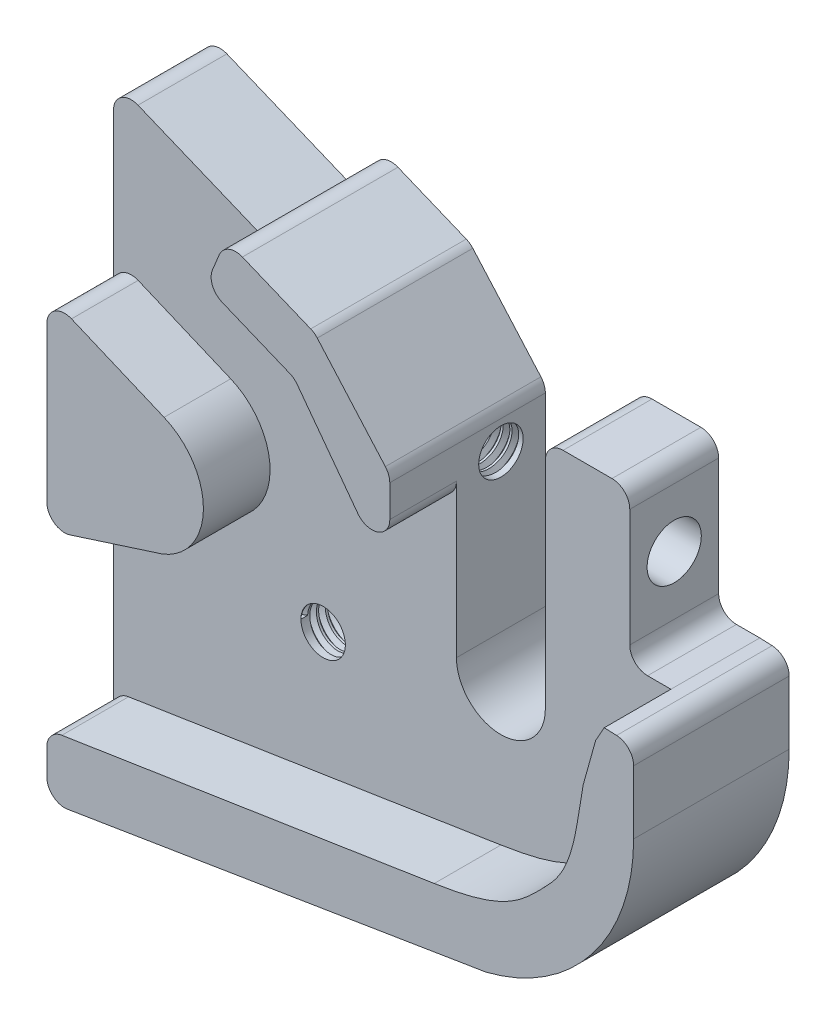
SolidWorks part; units mm, degrees
ref_plane "Front Plane" through (0, 0, 0) normal (0, 0, 1) x (1, 0, 0)
ref_plane "Top Plane" through (0, 0, 0) normal (0, 1, 0) x (1, 0, 0)
ref_plane "Right Plane" through (0, 0, 0) normal (1, 0, 0) x (0, 0, -1)
sketch "Sketch1" plane through (0, 0, 0) normal (0, 0, 1) x (1, 0, 0)
  line L0 (-48.8998, -64.1664) -> (-34.4801, 53.9567) construction
  line L3 (0, 51.4823) -> (78.4652, 51.4823)
  line L4 (78.4652, 0) -> (78.4652, 51.4823)
  line L5 (-0.9054, 14.8469) -> (9.0946, 14.8469)
  line L6 (9.0946, 14.8469) -> (9.0946, -2.1531)
  line L7 (9.0946, -2.1531) -> (-0.9054, -2.1531)
  line L8 (-0.9054, -2.1531) -> (-0.9054, 14.8469)
  line L9 (-11.6542, 28.4583) -> (-0.9054, 14.02)
  line L10 (-52.5896, 45.2866) -> (-11.6542, 28.4583)
  line L11 (9.0946, 14.8469) -> (9.0946, 29.052)
  line L12 (9.0946, 29.052) -> (18.5946, 29.052)
  line L13 (-61.5112, 32.1478) -> (-26.3036, 17.3197)
  line L14 (-26.3036, 17.3197) -> (-29.1124, 10.6505)
  line L15 (-29.1124, 10.6505) -> (-31.9213, 3.9813)
  line L16 (-70.304, -10.1797) -> (-26.4323, 3.9286)
  line L17 (-39.4934, 22.8747) -> (-39.4934, -0.2716)
  line L18 (-26.4323, 3.9286) -> (-29.1124, 10.6505)
  line L19 (-29.1124, 10.6505) -> (-31.7926, 17.3724)
  line L20 (4.0946, -12.9031) -> (-39.4934, -19.6726)
  line L22 (23.2246, 11.8381) -> (22.2572, 10.123)
  line L23 (23.2246, 11.8381) -> (34.7443, 11.3546)
  line L24 (-0.9054, 14.8469) -> (-0.9054, 20.5391)
  line L25 (-19.3381, 38.1043) -> (-8.9222, 33.8224)
  line L26 (-11.6542, 28.4583) -> (-9.3728, 34.0076)
  line L27 (-7.3088, 22.6214) -> (-2.496, 26.2043)
  line L28 (-2.496, 26.2043) -> (-9.3728, 34.0076)
  line L29 (-70.5009, -25.054) -> (-69.6167, -30.4821)
  line L31 (26.529, 2.6512) -> (26.529, -15.9236)
  line L32 (27.019, 6.583) -> (34.7443, 6.583)
  line L33 (34.7443, 6.583) -> (34.7443, 11.3546)
  line L34 (-11.6542, 28.4583) -> (-8.9222, 28.4583)
  line L35 (-70.5009, -25.054) -> (-70.304, -10.1797)
  line L36 (18.5946, 29.052) -> (18.5946, 11.8381)
  line L37 (-39.4934, -0.2716) -> (-39.4934, -26.678)
  line L38 (-39.4934, 22.8747) -> (-39.4934, 39.9028)
  line L39 (22.2572, 10.123) -> (21.4546, 7.2463)
  line L40 (21.4546, 7.2463) -> (20.8501, 5.08)
  line L41 (20.8501, 5.08) -> (20.5233, 3.0772)
  line L42 (-8.9222, 28.4583) -> (-8.9222, 25.2921)
  line L43 (-19.3381, 38.1043) -> (-21.6194, 32.5549)
  line L44 (-0.9054, 20.5391) -> (-0.9054, 24.0677)
  line L45 (-2.496, 26.2043) -> (-0.9054, 24.3993)
  line L46 (-21.6194, 32.5549) -> (-27.6495, 17.8865)
  line L47 (-39.4934, -26.678) -> (29.4812, -15.4427)
  line L48 (4.5907, 2.6512) -> (19.4637, 2.6512) construction
  line L49 (19.4637, 2.6512) -> (26.529, 2.6512) construction
  line L50 (26.529, 2.6512) -> (26.529, 6.583)
  line L51 (26.529, 6.583) -> (27.019, 6.583)
  line L52 (-0.9054, 24.3993) -> (-0.9054, 24.0677)
  line L53 (18.5946, 11.8381) -> (23.2246, 11.8381)
  line L54 (4.0946, -2.1531) -> (-15.9054, -2.1531)
  line L55 (26.529, 6.583) -> (26.529, 11.6994)
  line L56 (4.0946, -2.1531) -> (4.0946, -12.9031) construction
  circle A0 centre (4.0946, 2.8469) radius 5
  circle A1 centre (4.0946, 9.8469) radius 5
  circle A2 centre (-29.1124, 10.6505) radius 7.2365
  circle A4 centre (4.5907, 2.6512) radius 21.9383
  circle A5 centre (-15.9054, -2.1531) radius 3
  spline S0 degree 3 poles (4.0946, -12.9031) (7.1977, -12.407) (12.0844, -11.481) (15.9679, -7.6449) (18.0516, -5.4431) (19.7772, -1.9974) (20.1723, 1.0102) (20.5233, 3.0772) knots 0 0 0 0 0.38814 0.547132 0.64369 0.748457 1 1 1 1
  dimension "D4" = 9.5
  dimension "D7" = 6
  dimension "D1" = 119
  dimension "D2" = 10
  dimension "D3" = 17
  dimension "D5" = 18
  dimension "D6" = 6
extrude "Boss-Extrude2" add sketch "Sketch1" along normal blind 10 contours A5 A4 L9 L10 L46 L13 A2 L16 L37 L20 | L46 L10 L38 L13 | A2 L13 L17 L16 | A4 L20 L37 L47 | S0 L20 A4 L47 L23 L22 L39 L40 L41 | L20 S0 L41 L40 L39 L22 L53 L36 A4 L11 L6 L7 L54 A5 | A5 L54 L8 L9 A4 | A0 L8 L7 | A0 L7 L6 | L44 A4 L9 L8 L24 | L27 L28 L26 L9 | A4 L44 L52 L45 L27 L9 | L25 L43 L10 L26 | A4 L36 L12 L11 | A4 L50 L55 L23 | A4 A5 | A5 A4 | A2 region at (-2.8071, 19.9148, 0) region at (-8.3031, 7.9581, 0) region at (9.6471, 19.4845, 0) region at (-23.6657, 2.4269, 0) region at (-3.9237, 23.8565, 0) region at (14.3748, 25.5507, 0) region at (7.9778, -1.0363, 0) region at (0.2115, -1.0363, 0) region at (-7.5395, 27.8934, 0) region at (-15.0859, -1.961, 0) region at (-17.5867, -2.5472, 0) region at (-15.4961, 33.2813, 0) region at (25.5669, 7.2243, 0) region at (25.9377, 9.4895, 0) region at (-31.952, 28.8341, 0) region at (-21.3324, -20.4818, 0) region at (-26.9869, 17.5785, 0)
extrude "Boss-Extrude3" add sketch "Sketch1<7>" along normal blind 17.5 contours A2 L13 L17 L16 | L25 L43 L10 L26 | L27 L28 L26 L9 | A4 L44 L52 L45 L27 L9 | L44 A4 L9 L8 L24 | A4 L20 L37 L47 | S0 L20 A4 L47 L23 L22 L39 L40 L41 | A4 L50 L55 L23 | A2 region at (-2.8071, 19.9148, 0) region at (-3.9237, 23.8565, 0) region at (-7.5395, 27.8934, 0) region at (-15.4961, 33.2813, 0) region at (25.5669, 7.2243, 0) region at (25.9377, 9.4895, 0) region at (-21.3324, -20.4818, 0) region at (-26.9869, 17.5785, 0)
sketch "Sketch1<7>" plane through (0, 0, 0) normal (0, 0, 1) x (1, 0, 0) same geometry as "Sketch1"
sketch "Sketch2" plane through (18.5946, 0, 0) normal (1, 0, 0) x (0, 0, -1)
  line L0 (-5, 29.052) -> (-5, 20.445) construction
  line L1 (-10, 29.052) -> (0, 29.052) construction
  line L2 (-10, 20.445) -> (-5, 20.445) construction
  line L3 (-10, 29.052) -> (-10, 11.8381) construction
  circle A0 centre (-5, 20.445) radius 3.05
  dimension "D1" = 6.1
hole_wizard "Tap Drill for M6x1.0 Tap3" positions "3DSketch3" profile "Sketch7" hole size "M6x1.0" standard "ANSI Metric"
sketch3d "3DSketch3"
  point P0 (18.5946, 20.445, 5)
sketch "Sketch7" plane through (18.5946, 20.445, 5) normal (0, 1, 0) x (0, 0, -1)
  line L0 (0, 0) -> (0, 44.5022)
  line L1 (0, 44.5022) -> (2.5, 43)
  line L2 (2.5, 43) -> (2.5, 0)
  line L5 (2.5, 0) -> (0, 0)
  line L10 (0, 44.5022) -> (-2.5, 43) construction
  line L11 (0, -6.35) -> (0, 107.95) construction
  dimension "Hole Dia." = 5
  dimension "Hole Depth" = 43
  dimension "Drill Angle" = 118
fillet "Fillet1" radius 2 15 edges at (-39.4934, -0.2716, 13.75) (-39.4934, -26.678, 8.75) (-0.9054, 14.02, 13.75) (-21.6194, 32.5549, 13.75) (-19.3381, 38.1043, 8.75) (-9.3728, 34.0076, 8.75) (9.0946, 29.052, 5) (18.5946, 29.052, 5) (18.5946, 11.8381, 5) (-0.9054, 24.3993, 8.75) (-39.4934, 39.9028, 5) (-39.4934, 22.8747, 13.75) (-11.6542, 28.4583, 13.75) (26.529, 11.6994, 8.75) (-39.4934, -19.6726, 13.75)
hole_wizard "Tap Drill for M6x1.0 Tap2" positions "3DSketch2" profile "Sketch5" hole size "M6x1.0" standard "ANSI Metric" end condition through all
sketch3d "3DSketch2"
  line L0 (4.0946, -2.1531, 10) -> (-15.9054, -2.1531, 10)
  arc A0 (-0.9054, 2.8469, 10) -> (9.0946, 2.8469, 10) centre (4.0946, 2.8469, 10) ccw construction
  point P0 (-15.9054, -2.1531, 10)
  point P8 (4.0946, 2.8469, 15)
  dimension "D1" = 20
sketch "Sketch5" plane through (-15.9054, -2.1531, 10) normal (1, 0, 0) x (0, -1, 0)
  line L0 (0, 0) -> (0, 10)
  line L1 (0, 10) -> (2.5, 10)
  line L2 (2.5, 10) -> (2.5, 0)
  line L5 (2.5, 0) -> (0, 0)
  line L11 (0, -6.35) -> (0, 107.95) construction
  dimension "Thru Hole Dia." = 5
  dimension "Thru Hole Depth" = 10
thread "Thread1" pitch 1 method cut profile "Thread Profile2" start angle 0, offset 0, length 23, pitch 1, diameter 5
ref_plane "Plane2" through (-0.9054, 20.445, 7.5) normal (0, -1, 0) x (0, 0, 1)
sketch "Thread Profile2" plane through (-0.9054, 20.445, 7.5) normal (0, -1, 0) x (0, 0, 1)
  line L0 (0, 0) -> (0, 1) construction
  line L1 (0, 0) -> (0.5413, 0.3125)
  line L2 (0.5413, 0.3125) -> (0.5413, 0.4375)
  line L3 (0.5413, 0.4375) -> (0, 0.75)
  line L4 (0.5413, 0.375) -> (0, 0.375) construction
  line L11 (0, 0) -> (0, 0.75)
  point P2 (0, 0)
  dimension "Pitch" = 1
  dimension "Profile_Angle" = 60
  dimension "Profile_Land" = 0.125
  dimension "Profile_Height" = 0.5413
extrude "Cut-Extrude2" cut sketch "Sketch2" against normal blind 10 contours A0
thread "Thread2" pitch 1 method cut profile "Thread Profile3" start angle 0, offset 0, length 13, pitch 1, diameter 5
ref_plane "Plane3" through (-18.4054, -2.1531, 10) normal (0, -1, 0) x (-1, 0, 0)
sketch "Thread Profile3" plane through (-18.4054, -2.1531, 10) normal (0, -1, 0) x (-1, 0, 0)
  line L0 (0, 0) -> (0, 1) construction
  line L1 (0, 0) -> (0.5413, 0.3125)
  line L2 (0.5413, 0.3125) -> (0.5413, 0.4375)
  line L3 (0.5413, 0.4375) -> (0, 0.75)
  line L4 (0.5413, 0.375) -> (0, 0.375) construction
  line L11 (0, 0) -> (0, 0.75)
  point P2 (0, 0)
  dimension "Pitch" = 1
  dimension "Profile_Angle" = 60
  dimension "Profile_Land" = 0.125
  dimension "Profile_Height" = 0.5413
